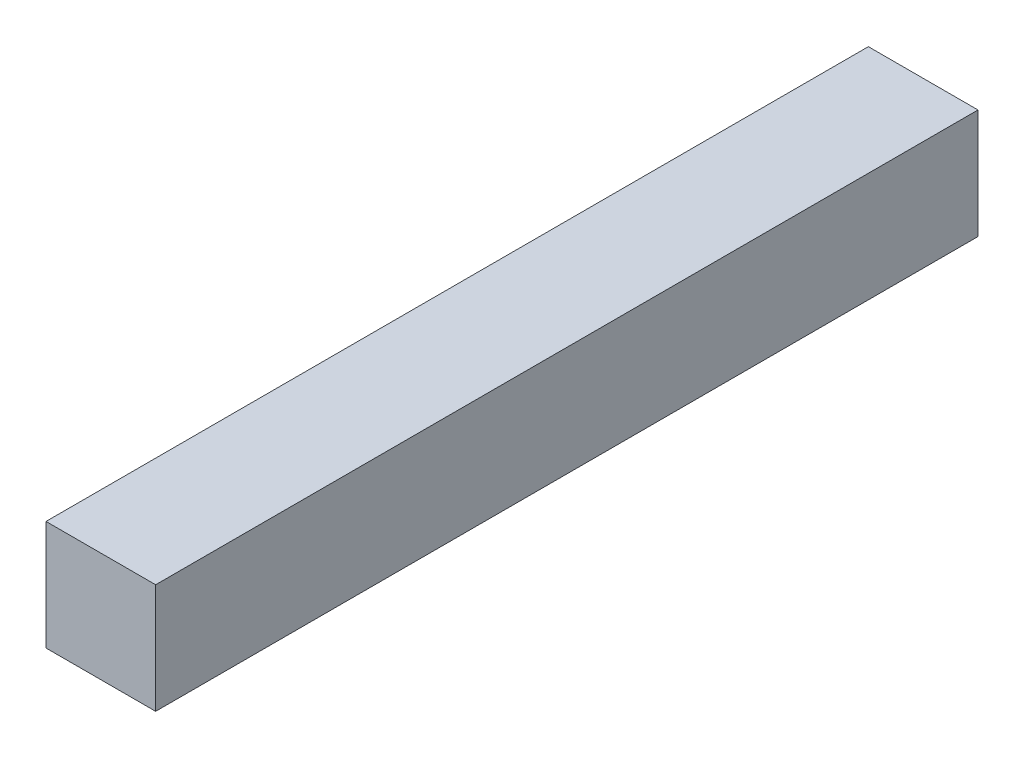
SolidWorks part; units mm, degrees
ref_plane "前视基准面" through (0, 0, 0) normal (0, 0, 1) x (1, 0, 0)
ref_plane "上视基准面" through (0, 0, 0) normal (0, 1, 0) x (1, 0, 0)
ref_plane "右视基准面" through (0, 0, 0) normal (1, 0, 0) x (0, 0, -1)
other "Configuration Table"
sketch "Sketch1" plane through (0, 0, 0) normal (0, 0, 1) x (1, 0, 0)
  line L1 (-25, -25) -> (25, -25)
  line L2 (-25, -25) -> (-25, 25)
  line L3 (-25, 25) -> (25, 25)
  line L4 (25, -25) -> (25, 25)
  line L5 (-25, -25) -> (25, 25) construction
  line L6 (-25, 25) -> (25, -25) construction
  point P0 (0, 0)
extrude "Boss-Extrude1" add sketch "Sketch1" along normal blind 375
ref_plane "Plane1" through (0, 0, 375) normal (0, 0, 1) x (1, 0, 0)
sketch "Sketch2" plane through (0, 0, 375) normal (0, 0, 1) x (1, 0, 0)
  circle A0 centre (0, 0) radius 4.25
ref_plane "top_end_face" through (0, 0, 375) normal (0, 0, 1) x (1, 0, 0)
ref_plane "Plane3" through (25, 0, 0) normal (1, 0, 0) x (0, 0, -1)
ref_plane "side_face_x" through (25, 0, 0) normal (1, 0, 0) x (0, 0, -1)
ref_plane "Plane5" through (0, 25, 0) normal (0, 1, 0) x (1, 0, 0)
ref_plane "side_face_y" through (0, 25, 0) normal (0, 1, 0) x (1, 0, 0)
sketch3d "3DSketch1"
  line L0 (0, 0, 375) -> (0, 0, 355) construction
ref_axis "leg_hole_axis" through (0, 0, 375) along (0, 0, -1)
